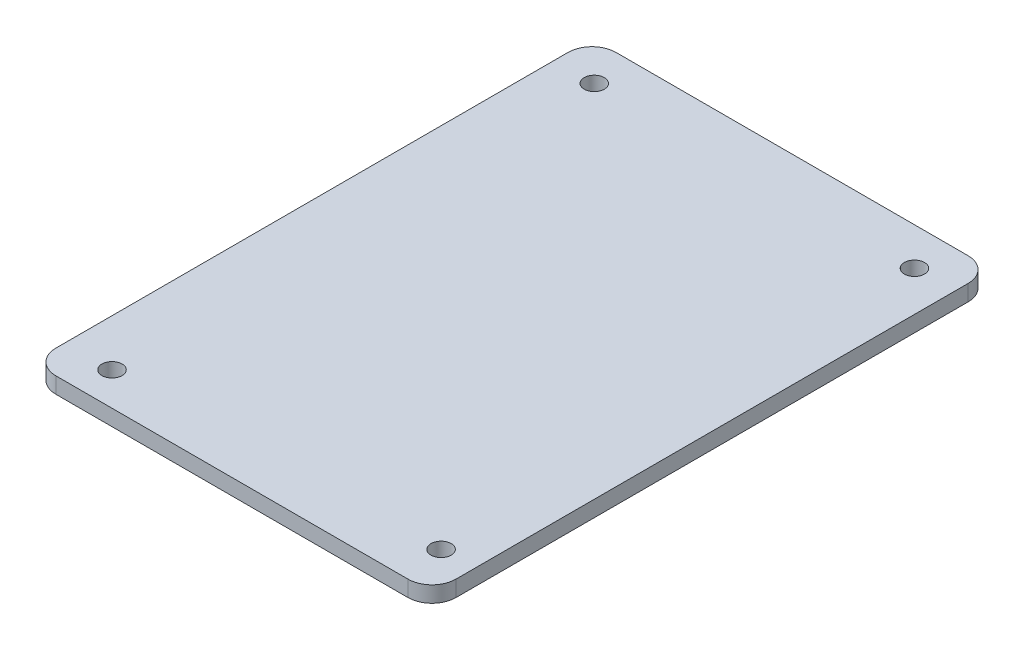
SolidWorks part; units mm, degrees
ref_plane "前视基准面" through (0, 0, 0) normal (0, 0, 1) x (1, 0, 0)
ref_plane "上视基准面" through (0, 0, 0) normal (0, 1, 0) x (1, 0, 0)
ref_plane "右视基准面" through (0, 0, 0) normal (1, 0, 0) x (0, 0, -1)
other "Configuration Table"
sketch "草图1" plane through (0, 0, 0) normal (0, 1, 0) x (1, 0, 0)
  line L0 (0, 48.4697) -> (0, -48.4697) construction
  line L1 (-25, -35) -> (25, -35)
  line L2 (-25, -35) -> (-25, 35)
  line L3 (-25, 35) -> (25, 35)
  line L4 (25, -35) -> (25, 35)
  line L5 (-25, -35) -> (25, 35) construction
  line L6 (-25, 35) -> (25, -35) construction
  line L7 (-42.3315, -0.5959) -> (42.3315, 0.5959) construction
  circle A0 centre (20.0079, 30.2876) radius 1.26
  circle A1 centre (-20.0079, 30.2876) radius 1.26
  circle A2 centre (20.8526, -29.7124) radius 1.26
  circle A3 centre (-19.1474, -30.8388) radius 1.26
  point P0 (0, 0)
  dimension "D3" = 2.52
  dimension "D5" = 60
  dimension "D1" = 50
  dimension "D2" = 70
  dimension "D4" = 40
extrude "凸台-拉伸1" add sketch "草图1" along normal blind 2
fillet "圆角1" radius 3 4 edges at (-25, 1, -35) (25, 1, -35) (-25, 1, 35) (25, 1, 35)
